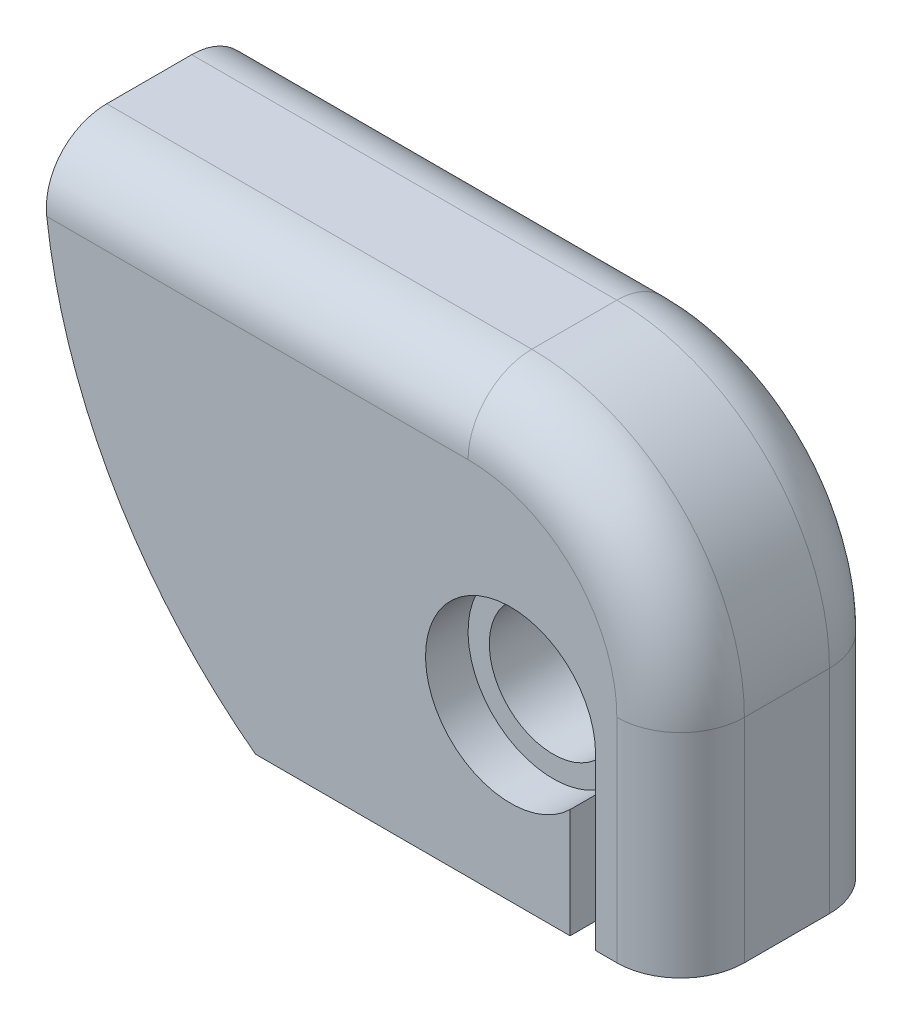
SolidWorks part; units mm, degrees
material "ABS"
ref_plane "Front Plane" through (0, 0, 0) normal (0, 0, 1) x (1, 0, 0)
ref_plane "Top Plane" through (0, 0, 0) normal (0, 1, 0) x (1, 0, 0)
ref_plane "Right Plane" through (0, 0, 0) normal (1, 0, 0) x (0, 0, -1)
sketch "Sketch1" plane through (0, 0, 0) normal (0, 0, 1) x (1, 0, 0)
  line L1 (0, 0) -> (0, 10)
  line L2 (-15, 10) -> (-15, 11.9358) construction
  line L3 (0, 10) -> (-15, 10)
  line L4 (0, 0) -> (-10, 0)
  arc A0 (-15, 10) -> (-10, 0) centre (-2.5, 10) ccw
  dimension "D1" = 15
  dimension "D2" = 10
  dimension "D3" = 10
extrude "Extrude1" add sketch "Sketch1" along normal mid plane 5
sketch "Sketch2" plane through (0, 0, 0) normal (0, 0, 1) x (1, 0, 0)
  line L0 (0, 4) -> (-4, 4) construction
  line L1 (0, 0) -> (0, 10) construction
  line L2 (-4, 4) -> (-4, 0) construction
  line L4 (0, 10) -> (-15, 10) construction
  line L5 (0, 5) -> (0, 10)
  line L6 (0, 0) -> (-10, 0) construction
  line L7 (0, 10) -> (-5, 10)
  circle A0 centre (-4, 4) radius 1.5
  arc A1 (0, 5) -> (-5, 10) centre (-5, 5) ccw
  dimension "D2" = 3
  dimension "D3" = 5
  dimension "D1" = 4
extrude "Extrude2" cut sketch "Sketch2" against normal up to surface (2.5 mm away) from surface up to face at (-6.5451, 4.8525, -2.5) starting at face at (-6.5451, 4.8525, 2.5)
sketch "Sketch3" plane through (0, 0, 0) normal (0, 0, 1) x (1, 0, 0)
  line L0 (-2, 4) -> (-2, 0)
  line L3 (0, 0) -> (-10, 0) construction
  line L4 (-2.6, 2.5717) -> (-2.6, 0)
  line L5 (-2.6, 0) -> (-2, 0)
  circle A0 centre (-4, 4) radius 2
  dimension "D2" = 4
  dimension "D1" = 0.6
extrude "Extrude3" cut sketch "Sketch3" along normal blind 1 from vertex contours A0 | A0 region at (-4, 4, 0) region at (-2.2815, 1.5257, 0) starting at point (-10, 0, -2.5)
extrude "Extrude4" cut sketch "Sketch3<3>" against normal blind 1 from vertex contours A0 | A0 region at (-4, 4, 0) region at (-2.2815, 1.5257, 0) starting at point (0, 0, 2.5)
sketch "Sketch3<3>" plane through (0, 0, 0) normal (0, 0, 1) x (1, 0, 0) same geometry as "Sketch3"
fillet "Fillet1" radius 1.5 6 edges at (0, 2.5, 2.5) (-1.4645, 8.5355, 2.5) (-10, 10, -2.5) (0, 2.5, -2.5) (-10, 10, 2.5) (-1.4645, 8.5355, -2.5)
